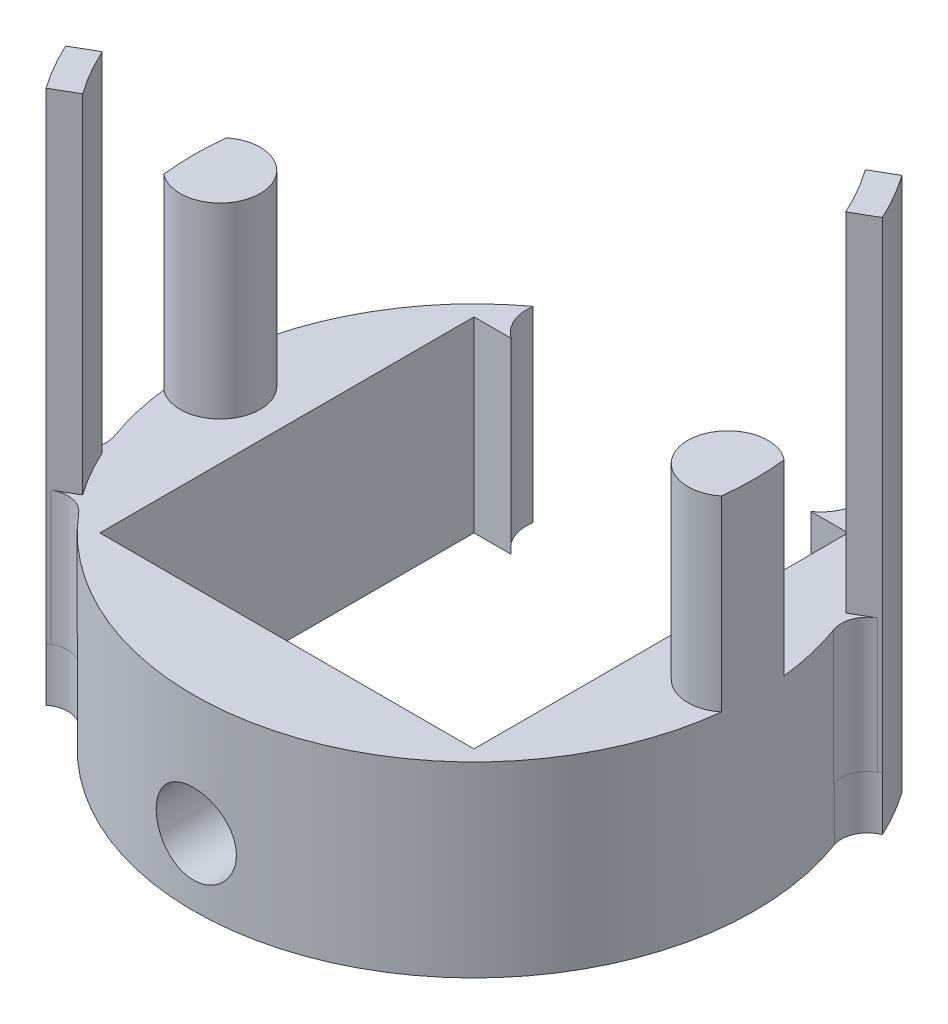
SolidWorks part; units mm, degrees
ref_plane "Front Plane" through (0, 0, 0) normal (0, 0, 1) x (1, 0, 0)
ref_plane "Top Plane" through (0, 0, 0) normal (0, 1, 0) x (1, 0, 0)
ref_plane "Right Plane" through (0, 0, 0) normal (1, 0, 0) x (0, 0, -1)
sketch "Sketch1" plane through (0, 0, 0) normal (0, 1, 0) x (1, 0, 0)
  line L0 (0, 0) -> (7, 0)
  line L1 (7, 0) -> (7, 7)
  line L2 (7, 7) -> (-7, 7)
  line L3 (-7, 7) -> (-7, -7)
  line L4 (-7, -7) -> (7, -7)
  line L5 (7, -7) -> (7, 0)
  circle A0 centre (0, 0) radius 10.5
extrude "Boss-Extrude1" add sketch "Sketch1" along normal blind 7 contours A0 L5 L4 L3 L2 L1
sketch "Sketch2" plane through (0, 7, 0) normal (0, 1, 0) x (1, 0, 0)
  line L0 (0, 0) -> (-9.5, 0)
  line L1 (0, 0) -> (9.5, 0)
  circle A0 centre (-9.5, 0) radius 1.5
  circle A1 centre (9.5, 0) radius 1.5
extrude "Boss-Extrude2" add sketch "Sketch2" along normal blind 7
sketch "Sketch4" plane through (0, 7, 0) normal (0, 1, 0) x (1, 0, 0)
  line L0 (-5.1962, -3) -> (5.1962, 3)
  line L2 (5.1962, 3) -> (10.3923, 6)
  line L3 (0, 0) -> (0.5, -0.866)
  line L4 (-10.3253, -7.116) -> (11.3253, 5.384)
  line L5 (11.3253, 5.384) -> (10.3253, 7.116)
  line L6 (10.3253, 7.116) -> (-11.3253, -5.384)
  line L7 (-0.5, 0.866) -> (0, 0)
  line L8 (-10.3253, -7.116) -> (-11.3253, -5.384)
  line L9 (-5.1962, -3) -> (-10.3923, -6)
  circle A0 centre (7.7942, 4.5) radius 3
  circle A1 centre (-7.7942, -4.5) radius 3
  arc M10 (-10.4342, -1.1736) -> (10.4342, -1.1736) centre (0, 0) ccw
  arc M12 (10.4342, 1.1736) -> (-10.4342, 1.1736) centre (0, 0) ccw
  line M14 (7, 7) -> (7, -7)
  line M16 (-7, -7) -> (-7, 7)
extrude "Boss-Extrude4" add sketch "Sketch4" against normal blind 5 contours A1 L9 L6 M10 | L9 L6 M16 M10 | L9 L4 M16 M10 | A1 L4 L9 M10 | L2 A0 L6 M12 | L4 A0 L2 M12 | L6 L2 M12 M14 | L4 L2 M14 M12
sketch "Sketch5" plane through (0, 7, 0) normal (0, 1, 0) x (1, 0, 0)
  line L0 (0, 0) -> (10.3923, 6)
  line L1 (10.3923, 6) -> (9.5, 0)
  line L2 (10.3923, 6) -> (4.75, 8.2272)
  line L3 (0, 0) -> (-4.75, 8.2272)
  line L4 (9.5, 0) -> (-9.5, 0)
  arc A0 (10.7437, 5.0482) -> (9.7437, 6.7802) centre (7.7942, 4.5) ccw construction
  circle A1 centre (4.75, 8.2272) radius 1.5
  circle A2 centre (-4.75, 8.2272) radius 1.5
  circle A3 centre (-4.75, -8.2272) radius 1.5
  circle A4 centre (4.75, -8.2272) radius 1.5
extrude "Cut-Extrude2" cut sketch "Sketch5" against normal blind 5
sketch "Sketch6" plane through (0, 7, 0) normal (0, 1, 0) x (1, 0, 0)
  line L0 (-10.7437, -5.0482) -> (9.7437, 6.7802)
  line L1 (10.7437, 5.0482) -> (-9.7437, -6.7802)
  circle A0 centre (0, 0) radius 10.5
  arc A1 (-10.7437, -5.0482) -> (-9.7437, -6.7802) centre (-7.7942, -4.5) ccw
  arc A2 (9.7437, 6.7802) -> (10.7437, 5.0482) centre (7.7942, 4.5) cw
  line M12 (-9.5519, -4.3601) -> (-10.7437, -5.0482)
  arc M13 (-10.7437, -5.0482) -> (-9.7437, -6.7802) centre (-7.7942, -4.5) ccw
  line M14 (-9.7437, -6.7802) -> (-8.5519, -6.0922)
  line M18 (9.5519, 4.3601) -> (10.7437, 5.0482)
  arc M19 (10.7437, 5.0482) -> (9.7437, 6.7802) centre (7.7942, 4.5) ccw
  line M20 (9.7437, 6.7802) -> (8.5519, 6.0922)
extrude "Boss-Extrude5" add sketch "Sketch6" along normal blind 13 contours A0 M12 M13 M14 | A0 M18 M19 M20
sketch "Sketch8" plane through (0, 0, 0) normal (0, 0, 1) x (1, 0, 0)
  line L0 (-10.5, 14) -> (-10.5, 0) construction
  line L1 (10.5, 0) -> (-10.5, 0)
  line L2 (10.5, 0) -> (10.5, 5)
  line L3 (10.5, 5) -> (-10.5, 5)
  line L4 (-10.5, 0) -> (-10.5, 5)
  line L5 (-10.5, 5) -> (10.5, 0)
  circle A0 centre (0, 2.5) radius 1.25
extrude "Cut-Extrude4" cut sketch "Sketch8" against normal through all both and the other way through all contours L5 A0 | L5 A0
fillet "Fillet1" radius 1 4 edges at (-8.5519, 4.5, 6.0922) (-9.5519, 4.5, 4.3601) (8.5519, 4.5, -6.0922) (9.5519, 4.5, -4.3601)
sketch "Sketch9" plane through (0, 7, 0) normal (0, 1, 0) x (1, 0, 0)
  line L0 (-10.3923, -6) -> (-7.7942, -4.5)
  line L1 (-7.7942, -4.5) -> (0, 0)
  line L2 (0, 0) -> (-2.4499, 4.2434)
  circle A0 centre (0, 0) radius 11.5
  arc A1 (-10.7437, -5.0482) -> (-9.7437, -6.7802) centre (-7.7942, -4.5) ccw construction
  circle A2 centre (-7.7942, -4.5) radius 2.5
  circle A3 centre (7.7942, 4.5) radius 2.5
  circle A4 centre (0, 0) radius 15
extrude "Cut-Extrude5" cut sketch "Sketch9" along normal through all both and the other way through all
sketch "Sketch10" plane through (0, 0, 7) normal (0, 0, -1) x (-1, 0, 0)
  circle A0 centre (0, 2.5) radius 1.5
extrude "Cut-Extrude6" cut sketch "Sketch10" against normal blind 11.2
sketch "Sketch12" plane through (0, 2, 0) normal (0, 1, 0) x (1, 0, 0)
  circle A0 centre (4.75, 8.2272) radius 1.5
  circle A1 centre (-4.75, 8.2272) radius 1.5
  circle A2 centre (-0.1278, 8.4051) radius 4.653
  line M1 (3.8875, 7) -> (5.6125, 7)
  arc M2 (5.6125, 7) -> (6.2334, 8.4495) centre (4.75, 8.2272) ccw
  arc M3 (6.2334, 8.4495) -> (4.2008, 9.6231) centre (0, 0) ccw
  arc M4 (4.2008, 9.6231) -> (3.8875, 7) centre (4.75, 8.2272) ccw
extrude "Cut-Extrude7" cut sketch "Sketch12" against normal through all both and the other way through all contours A2 A1 | A1 A2 | A0 A2 A1 M4 | A2 M1 M3 M4 | A2 M1 M2 M3
sketch "Sketch13" plane through (0, 2, 0) normal (0, -1, 0) x (1, 0, 0)
  line L0 (9.9593, -5.75) -> (0, 0)
  line L1 (0, 0) -> (-1.2356, -2.1402)
  arc A0 (10.4216, -4.8622) -> (9.4216, -6.5942) centre (0, 0) cw
  arc A1 (10.4216, -4.8622) -> (9.8677, -3.5886) centre (10.7815, -3.9485) cw
  arc A2 (9.4216, -6.5942) -> (8.0417, -6.7514) centre (8.8102, -7.3628) ccw
  arc A3 (-10.4216, 4.8622) -> (-9.8677, 3.5886) centre (-10.7815, 3.9485) cw
  arc A4 (-9.4216, 6.5942) -> (-8.0417, 6.7514) centre (-8.8102, 7.3628) ccw
  arc A5 (-9.4216, 6.5942) -> (-10.4216, 4.8622) centre (0, 0) ccw
  circle A6 centre (0, 0) radius 10.5
  arc M3 (9.4216, -6.5942) -> (10.4216, -4.8622) centre (0, 0) ccw
  arc M6 (9.8677, -3.5886) -> (8.0417, -6.7514) centre (0, 0) cw
extrude "Boss-Extrude6" add sketch "Sketch13" along normal blind 2 contours A2 L0 M3 M6 | A1 L0 M3 M6 | A6 A4 A5 A3
